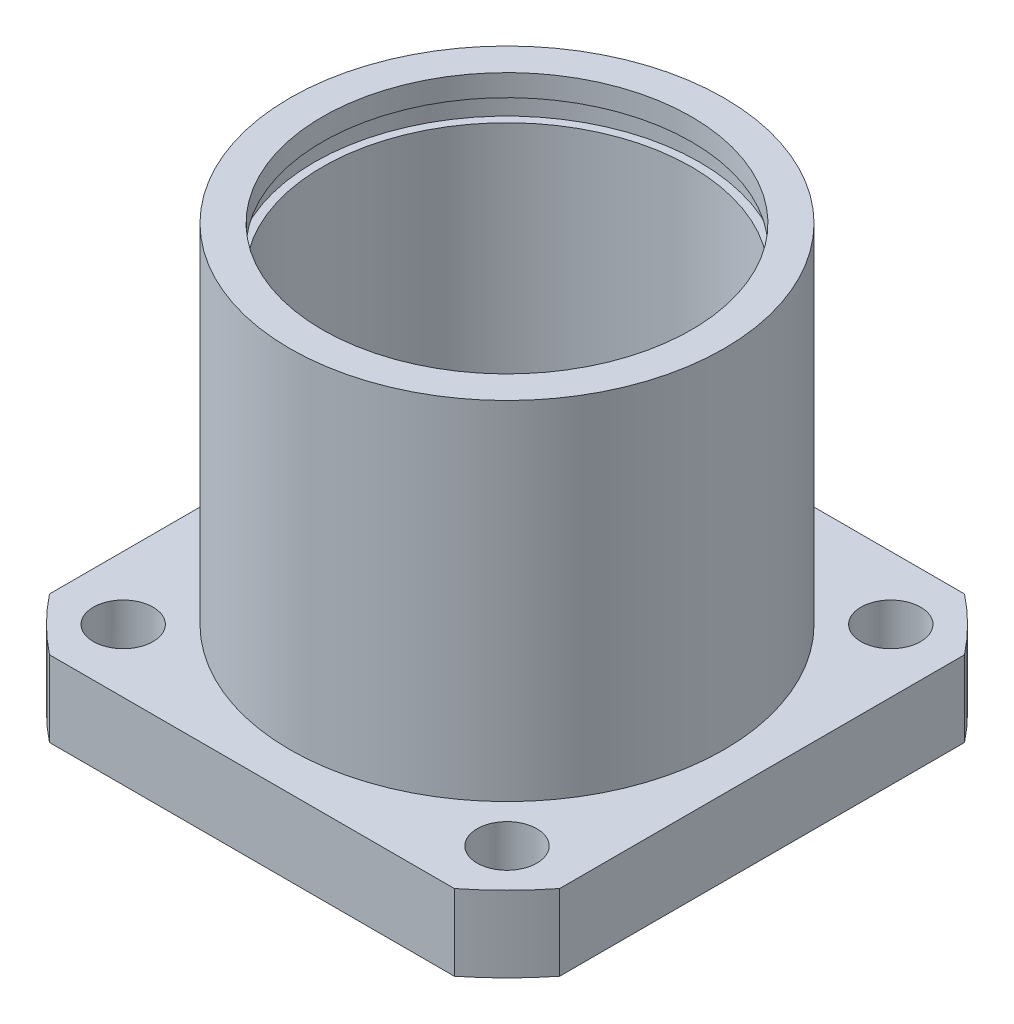
SolidWorks part; units mm, degrees
material "Сталь 45 ГОСТ 1050-88"
ref_plane "Спереди" through (0, 0, 0) normal (0, 0, 1) x (1, 0, 0)
ref_plane "Сверху" through (0, 0, 0) normal (0, 1, 0) x (1, 0, 0)
ref_plane "Справа" through (0, 0, 0) normal (1, 0, 0) x (0, 0, -1)
ref_axis "ОсьX" through (-88.99, 0, 0) along (1, 0, 0)
ref_axis "ОсьZ" through (0, 55, 0) along (0, -1, 0)
ref_axis "ОсьY" through (0, 0, -88.99) along (0, 0, 1)
sketch "Эскиз1" plane through (0, 0, 0) normal (0, 0, 1) x (1, 0, 0)
  line L0 (0, 50.2605) -> (0, -14.3325) construction
  line L1 (-17, 0) -> (-21.5, 0)
  line L2 (-30, 1) -> (-30, 8)
  line L3 (-30, 8) -> (-20, 8)
  line L4 (-20, 8) -> (-20, 40)
  line L5 (-20, 40) -> (-17, 40)
  line L6 (-17, 40) -> (-17, 38)
  line L7 (-17, 38) -> (-17.75, 38)
  line L8 (-17.75, 38) -> (-17.75, 36)
  line L9 (-17.75, 36) -> (-17, 36)
  line L10 (-17, 4) -> (-17.75, 4)
  line L11 (-17.75, 4) -> (-17.75, 2)
  line L12 (-17.75, 2) -> (-17, 2)
  line L13 (-17, 2) -> (-17, 0)
  line L14 (-17, 36) -> (-17, 4)
  line L15 (-21.5, 0) -> (-21.5, 1)
  line L16 (-21.5, 1) -> (-30, 1)
  dimension "D1" = 40
  dimension "D2" = 60
  dimension "D3" = 8
  dimension "D4" = 40
  dimension "D5" = 34
  dimension "D6" = 2
  dimension "D7" = 2
  dimension "D8" = 35.5
  dimension "D9" = 2
  dimension "D10" = 1
  dimension "D11" = 43
revolve "Повернуть1" add sketch "Эскиз1" angle 360 mid plane about L0
sketch "Эскиз4" plane through (0, 8, 0) normal (0, 1, 0) x (1, 0, 0)
  line L0 (-17.6777, 17.6777) -> (0, 0) construction
  line L1 (0, 0) -> (0, 25) construction
  circle A0 centre (-17.6777, 17.6777) radius 2.75
  circle A1 centre (-17.6777, -17.6777) radius 2.75
  circle A2 centre (17.6777, 17.6777) radius 2.75
  circle A3 centre (17.6777, -17.6777) radius 2.75
  circle A4 centre (0, 0) radius 25 construction
  dimension "D2" = 5.5
  dimension "D3" = 50
  dimension "D1" = 45
extrude "Вырез-Вытянуть1" cut sketch "Эскиз4" against normal through all
sketch "Эскиз5" plane through (0, 8, 0) normal (0, 1, 0) x (1, 0, 0)
  line L1 (23.5, 23.5) -> (-23.5, 23.5)
  line L2 (23.5, 23.5) -> (23.5, -23.5)
  line L3 (23.5, -23.5) -> (-23.5, -23.5)
  line L4 (-23.5, 23.5) -> (-23.5, -23.5)
  line L5 (23.5, 23.5) -> (-23.5, -23.5) construction
  line L6 (23.5, -23.5) -> (-23.5, 23.5) construction
  point P0 (0, 0)
  dimension "D1" = 47
extrude "Вырез-Вытянуть2" cut sketch "Эскиз5" against normal through all flip side to cut
